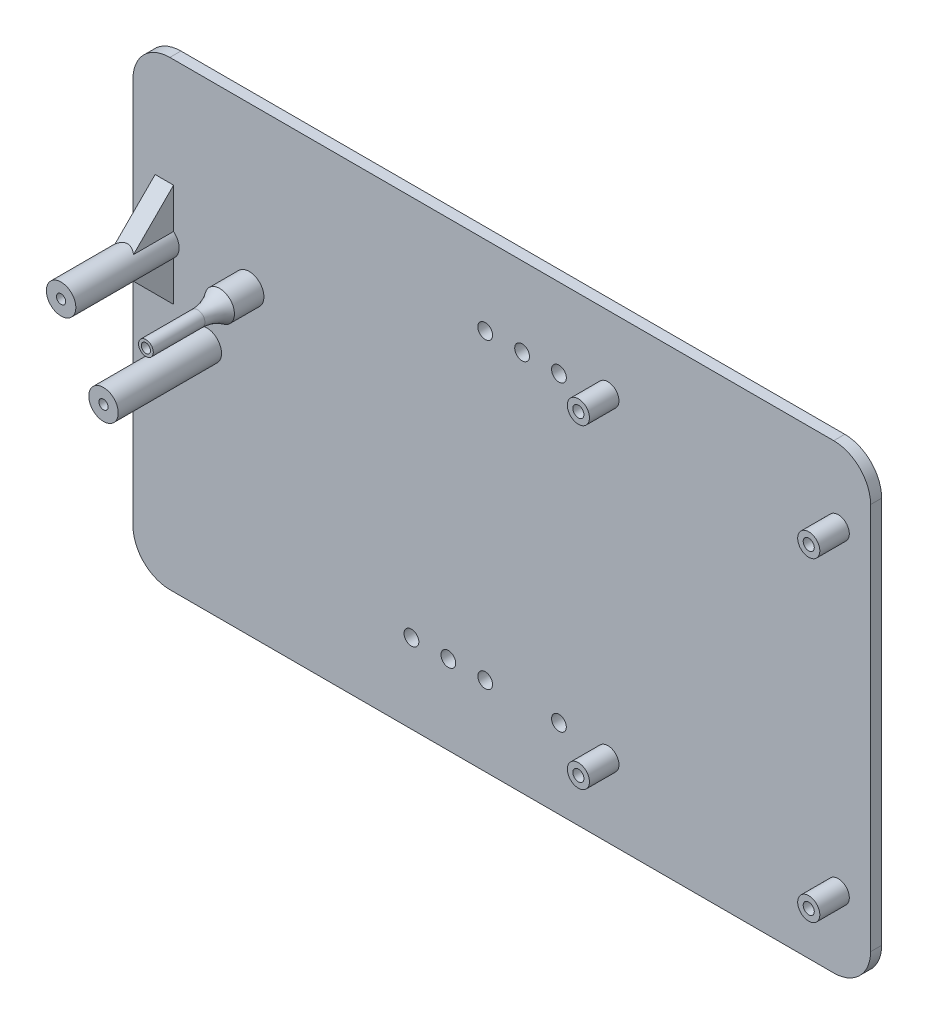
SolidWorks part; units mm, degrees
ref_plane "前视基准面" through (0, 0, 0) normal (0, 0, 1) x (1, 0, 0)
ref_plane "上视基准面" through (0, 0, 0) normal (0, 1, 0) x (1, 0, 0)
ref_plane "右视基准面" through (0, 0, 0) normal (1, 0, 0) x (0, 0, -1)
other "Configuration Table"
sketch "草图1" plane through (0, 0, 0) normal (0, 0, 1) x (1, 0, 0)
  line L1 (-100, -62.5) -> (100, -62.5)
  line L2 (-100, -62.5) -> (-100, 62.5)
  line L3 (-100, 62.5) -> (100, 62.5)
  line L4 (100, -62.5) -> (100, 62.5)
  line L5 (-100, -62.5) -> (100, 62.5) construction
  line L6 (-100, 62.5) -> (100, -62.5) construction
  point P0 (0, 0)
  dimension "D1" = 200
  dimension "D2" = 125
extrude "凸台-拉伸1" add sketch "草图1" along normal blind 3
sketch "草图2" plane through (0, 0, 3) normal (0, 0, 1) x (1, 0, 0)
  line L0 (-100, 0) -> (100, 0) construction
  line L1 (-100, 62.5) -> (-100, -62.5) construction
  line L2 (100, -62.5) -> (100, 62.5) construction
  line L3 (0, 62.5) -> (0, -62.5) construction
  line L4 (100, 62.5) -> (-100, 62.5) construction
  line L5 (-100, -62.5) -> (100, -62.5) construction
  line L7 (-94, -21) -> (-66, -21) construction
  line L8 (-94, -21) -> (-94, 21) construction
  line L9 (-94, 21) -> (-66, 21) construction
  line L10 (-66, -21) -> (-66, 21) construction
  line L11 (-94, -21) -> (-66, 21) construction
  line L12 (-94, 21) -> (-66, -21) construction
  line L13 (-91.5, -19) -> (-68.5, -19) construction
  line L14 (-91.5, -19) -> (-91.5, 19) construction
  line L15 (-91.5, 19) -> (-68.5, 19) construction
  line L16 (-68.5, -19) -> (-68.5, 19) construction
  line L17 (-91.5, -19) -> (-68.5, 19) construction
  line L18 (-91.5, 19) -> (-68.5, -19) construction
  circle A0 centre (-91.5, 19) radius 4
  circle A1 centre (-68.5, 19) radius 2
  circle A2 centre (-80, 0) radius 4
  point P12 (-80, 0)
  point P17 (-80, 0)
  dimension "D6" = 4
  dimension "D7" = 8
  dimension "D8" = 8
  dimension "D1" = 42
  dimension "D2" = 28
  dimension "D3" = 20
  dimension "D4" = 23
  dimension "D5" = 38
extrude "凸台-拉伸2" add sketch "草图2" along normal blind 28
sketch "草图3" plane through (0, 0, 31) normal (0, 0, 1) x (1, 0, 0)
  circle A0 centre (-91.5, 19) radius 1.25
  circle A1 centre (-68.5, 19) radius 1.25
  dimension "D1" = 2.5
  dimension "D2" = 2.5
extrude "切除-拉伸1" cut sketch "草图3" against normal blind 10
sketch "草图4" plane through (0, 0, 3) normal (0, 0, 1) x (1, 0, 0)
  line L0 (-100, 0) -> (100, 0) construction
  line L1 (-100, 62.5) -> (-100, -62.5) construction
  line L2 (100, -62.5) -> (100, 62.5) construction
  line L4 (-39.5, -41) -> (15.5, -41) construction
  line L5 (-39.5, -41) -> (-39.5, 41) construction
  line L6 (-39.5, 41) -> (15.5, 41) construction
  line L7 (15.5, -41) -> (15.5, 41) construction
  line L8 (-39.5, -41) -> (15.5, 41) construction
  line L9 (-39.5, 41) -> (15.5, -41) construction
  circle A0 centre (15.5, 41) radius 2
  circle A1 centre (15.5, -41) radius 2
  circle A2 centre (5.5, 41) radius 2
  circle A3 centre (-4.5, 41) radius 2
  circle A4 centre (-14.5, -41) radius 2
  circle A5 centre (-24.5, -41) radius 2
  circle A6 centre (-4.5, -41) radius 2
  point P6 (-12, 0)
  dimension "D1" = 4
  dimension "D5" = 4
  dimension "D6" = 4
  dimension "D7" = 4
  dimension "D11" = 4
  dimension "D12" = 4
  dimension "D14" = 4
  dimension "D2" = 82
  dimension "D3" = 55
  dimension "D4" = 12
  dimension "D8" = 10
  dimension "D9" = 10
  dimension "D10" = 15
  dimension "D13" = 10
  dimension "D15" = 10
extrude "切除-拉伸2" cut sketch "草图4" against normal through all
sketch "草图5" plane through (0, 0, 3) normal (0, 0, 1) x (1, 0, 0)
  line L0 (-100, 0) -> (100, 0) construction
  line L1 (-100, 62.5) -> (-100, -62.5) construction
  line L2 (100, -62.5) -> (100, 62.5) construction
  line L3 (0, 62.5) -> (0, -62.5) construction
  line L4 (100, 62.5) -> (-100, 62.5) construction
  line L5 (-100, -62.5) -> (100, -62.5) construction
  line L6 (60, 42.73) -> (60, -42.73) construction
  line L7 (26.1, 45.4) -> (93.9, 45.4) construction
  line L8 (26.1, 45.4) -> (26.1, -45.4) construction
  line L9 (26.1, -45.4) -> (93.9, -45.4) construction
  line L10 (93.9, 45.4) -> (93.9, -45.4) construction
  line L11 (26.1, 45.4) -> (93.9, -45.4) construction
  line L12 (26.1, -45.4) -> (93.9, 45.4) construction
  line L13 (28.77, -42.73) -> (91.23, -42.73) construction
  line L14 (28.77, -42.73) -> (28.77, 42.73) construction
  line L15 (28.77, 42.73) -> (91.23, 42.73) construction
  line L16 (91.23, -42.73) -> (91.23, 42.73) construction
  line L17 (28.77, -42.73) -> (91.23, 42.73) construction
  line L18 (28.77, 42.73) -> (91.23, -42.73) construction
  circle A0 centre (28.77, 42.73) radius 3
  circle A1 centre (28.77, -42.73) radius 3
  circle A2 centre (91.23, -42.73) radius 3
  circle A3 centre (91.23, 42.73) radius 3
  point P12 (60, 0)
  point P17 (60, 0)
  dimension "D6" = 6
  dimension "D7" = 6
  dimension "D1" = 90.8
  dimension "D2" = 67.8
  dimension "D3" = 40
  dimension "D4" = 2.67
  dimension "D5" = 2.67
extrude "凸台-拉伸3" add sketch "草图5" along normal blind 8
sketch "草图6" plane through (0, 0, 11) normal (0, 0, 1) x (1, 0, 0)
  circle A0 centre (28.77, 42.73) radius 1.5
  circle A1 centre (91.23, 42.73) radius 1.5
  circle A2 centre (28.77, -42.73) radius 1.5
  circle A3 centre (91.23, -42.73) radius 1.5
  dimension "D1" = 3
  dimension "D2" = 3
  dimension "D3" = 3
  dimension "D4" = 3
extrude "切除-拉伸3" cut sketch "草图6" against normal blind 8
fillet "圆角1" radius 10 4 edges at (100, -62.5, 1.5) (100, 62.5, 1.5) (-100, -62.5, 1.5) (-100, 62.5, 1.5)
sketch "草图8" plane through (0, 0, 3) normal (0, 0, 1) x (1, 0, 0)
  line L0 (-91.5, 19) -> (-91.5, 62.3869) construction
  line L1 (-68.5, 19) -> (-68.5, 62.5) construction
  line L2 (90, 62.5) -> (-90, 62.5) construction
  line L3 (-80, 0) -> (-80, 62.5) construction
  line L4 (28.77, -42.73) -> (28.77, 62.5) construction
  line L5 (91.23, -42.73) -> (91.23, 62.4241) construction
  arc A0 (-90, 62.5) -> (-100, 52.5) centre (-90, 52.5) ccw construction
  arc A1 (100, 52.5) -> (90, 62.5) centre (90, 52.5) ccw construction
ref_plane "基准面1" through (-91.5, 0, 0) normal (-1, 0, 0) x (0, 0, 1)
ref_plane "基准面2" through (-80, 0, 0) normal (-1, 0, 0) x (0, 0, 1)
ref_plane "基准面3" through (-68.5, 0, 0) normal (-1, 0, 0) x (0, 0, 1)
ref_plane "基准面4" through (28.77, 0, 0) normal (-1, 0, 0) x (0, 0, 1)
ref_plane "基准面5" through (91.23, 0, 0) normal (-1, 0, 0) x (0, 0, 1)
sketch "草图9" plane through (-91.5, 0, 0) normal (-1, 0, 0) x (0, 0, 1)
  line L0 (3, 33) -> (13, 23)
  line L1 (3, -42.73) -> (3, 62.4241) construction
  line L2 (31, 23) -> (3, 23) construction
  dimension "D1" = 10
  dimension "D2" = 135
rib "筋1" sketch "草图9" sketch "草图9" thickness 5 extrusion direction parallel to sketch draft on no parameters "D1"=5
sketch "草图10" plane through (-91.5, 0, 0) normal (-1, 0, 0) x (0, 0, 1)
  line L0 (13, 15) -> (3, 5)
  line L1 (3, 15) -> (31, 15) construction
  line L2 (3, -42.73) -> (3, 62.4241) construction
  dimension "D1" = 10
  dimension "D2" = 135
rib "筋2" sketch "草图10" sketch "草图10" thickness 5 extrusion direction parallel to sketch draft on no parameters "D1"=5
sketch "草图12" plane through (-68.5, 0, 0) normal (-1, 0, 0) x (0, 0, 1)
  line L0 (31, 17) -> (31, 21) construction
  line L4 (31, 17) -> (31, 21) construction
  line L6 (31, 21) -> (3, 21) construction
  line L7 (3, 19) -> (3, 62.5) construction
  line L8 (31, 17) -> (3, 17) construction
sketch "草图13" plane through (0, 0, 3) normal (0, 0, 1) x (1, 0, 0)
  circle A0 centre (-68.5, 19) radius 4
  dimension "D1" = 8
extrude "凸台-拉伸4" add sketch "草图13" along normal blind 8
fillet "圆角3" radius 10 1 edges at (-66.5, 19, 11)
sketch "草图14" plane through (0, 0, 31) normal (0, 0, 1) x (1, 0, 0)
  circle A0 centre (-80, 0) radius 1.25
  dimension "D1" = 2.5
extrude "切除-拉伸4" cut sketch "草图14" against normal blind 8
